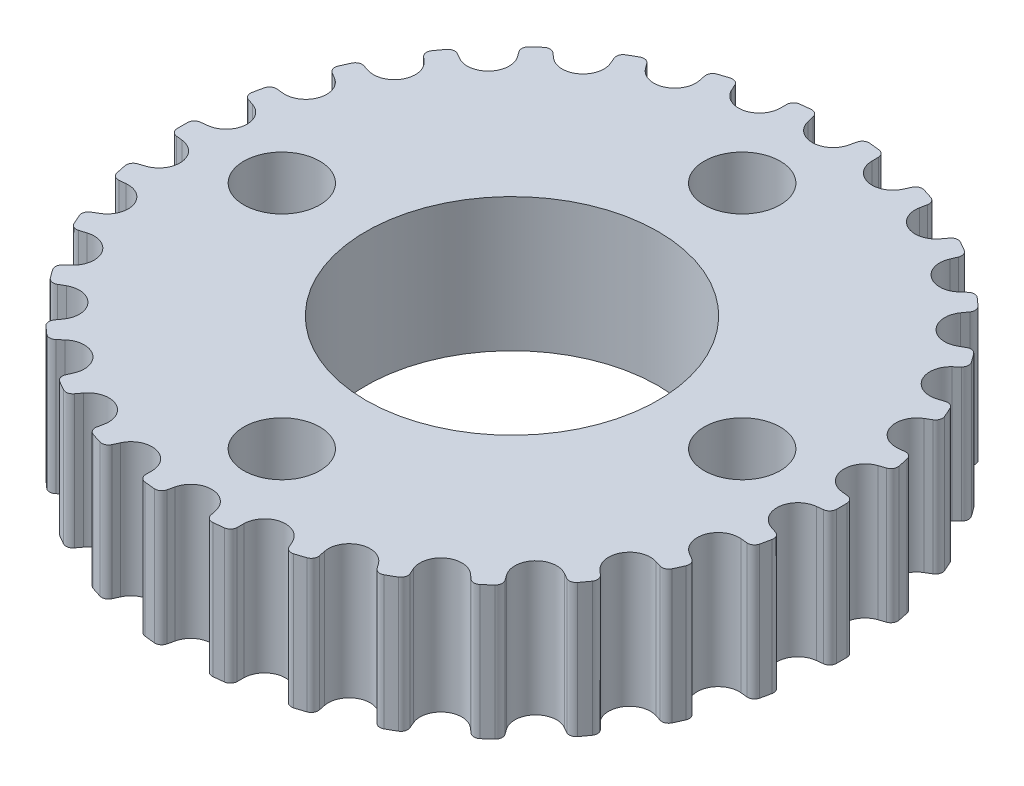
SolidWorks part; units mm, degrees
ref_plane "Front Plane" through (0, 0, 0) normal (0, 0, 1) x (1, 0, 0)
ref_plane "Top Plane" through (0, 0, 0) normal (0, 1, 0) x (1, 0, 0)
ref_plane "Right Plane" through (0, 0, 0) normal (1, 0, 0) x (0, 0, -1)
sketch "Sketch1" plane through (0, 0, 0) normal (0, 1, 0) x (1, 0, 0)
  circle A0 centre (0, 0) radius 14.3239
  dimension "D1" = 28.6479
extrude "Boss-Extrude1" add sketch "Sketch1" along normal blind 5.8
sketch "Sketch2" plane through (0, 5.8, 0) normal (0, 1, 0) x (1, 0, 0)
  line L0 (0, 0) -> (0, 14.3239) construction
  line L1 (-0.8883, 13.7564) -> (-0.95, 14.0339)
  line L2 (-2.9781, 14.0109) -> (-2.9781, 14.3239)
  line L3 (-2.9781, 14.3239) -> (2.9781, 14.3239)
  line L4 (0.8883, 13.7564) -> (0.95, 14.0339)
  line L5 (2.9781, 14.0109) -> (2.9781, 14.3239)
  circle A0 centre (0, 0) radius 14.3239 construction
  arc A1 (0.8883, 13.7564) -> (-0.8883, 13.7564) centre (0, 13.9539) cw
  arc A2 (-0.95, 14.0339) -> (-1.2694, 14.2676) centre (-1.2428, 13.9688) ccw
  arc A4 (0.95, 14.0339) -> (1.2694, 14.2676) centre (1.2428, 13.9688) cw
  arc A5 (-1.2694, 14.2676) -> (-2.9781, 14.0109) centre (0, 0) ccw
  arc A6 (1.2694, 14.2676) -> (2.9781, 14.0109) centre (0, 0) cw
  circle A8 centre (0, 0) radius 14.3239 construction
  point P11 (0, 14.3239)
  point P19 (0, 13.0439)
  dimension "D3" = 0.3
  dimension "D5" = 0.91
  dimension "D2" = 0.95
  dimension "D4" = 1.28
  dimension "D6" = 12
extrude "Cut-Extrude1" cut sketch "Sketch2" against normal through all
pattern_circular "CirPattern1" count 30 over 360 about axis through (0, 5.8, 0) along (0, -1, 0) of "Cut-Extrude1"
sketch "Sketch3" plane through (0, 0, 0) normal (0, -1, 0) x (1, 0, 0)
  circle A0 centre (0, 0) radius 6.35
  dimension "D1" = 12.7
extrude "Cut-Extrude2" cut sketch "Sketch3" against normal through all
sketch "Sketch4" plane through (0, 0, 0) normal (0, -1, 0) x (1, 0, 0)
  line L0 (0, 0) -> (0, 10) construction
  circle A0 centre (0, 10) radius 1.65
  circle A1 centre (10, 0) radius 1.65
  circle A2 centre (0, -10) radius 1.65
  circle A3 centre (-10, 0) radius 1.65
  point P5 (18.0031, -2.1436)
  point P6 (0, 0)
  point P14 (0, 0)
  dimension "D1" = 3.3
  dimension "D2" = 10
  dimension "D3" = 4
extrude "Cut-Extrude3" cut sketch "Sketch4" against normal through all
equation "\"smallPulleyTeeth\"= 15"
equation "\"largePulleyTeeth\"= 30"
equation "\"eighthThick\"= 2.9mm"
equation "\"D1@Sketch1\"=3*\"largePulleyTeeth\"/pi"
equation "\"D1@Boss-Extrude1\" = \"eighthThick\" * 2"
equation "\"D6@Sketch2\"=360/\"largePulleyTeeth\""
equation "\"quarterThick\"=5.6mm"
equation "\"D1@CirPattern1\"=\"largePulleyTeeth\""
equation "\"sixteenthThick\" = 1.7mm"
equation "\"OD\" = 150mm"
equation "\"puckAngle\" = 60.5deg"
equation "\"puckDiam\" = 76.5mm"
equation "\"axlePress\" = 5.8mm"
equation "\"press\" = 0.3mm"
equation "\"wheelClear\" = 0.3mm"
equation "\"10-32clear\" = 4.5mm"
equation "\"D1@Sketch4\"=\"6-32clear\""
equation "\"6-32clear\" = 3.3mm"
equation "\"8-32clear\" = 4.0mm"
